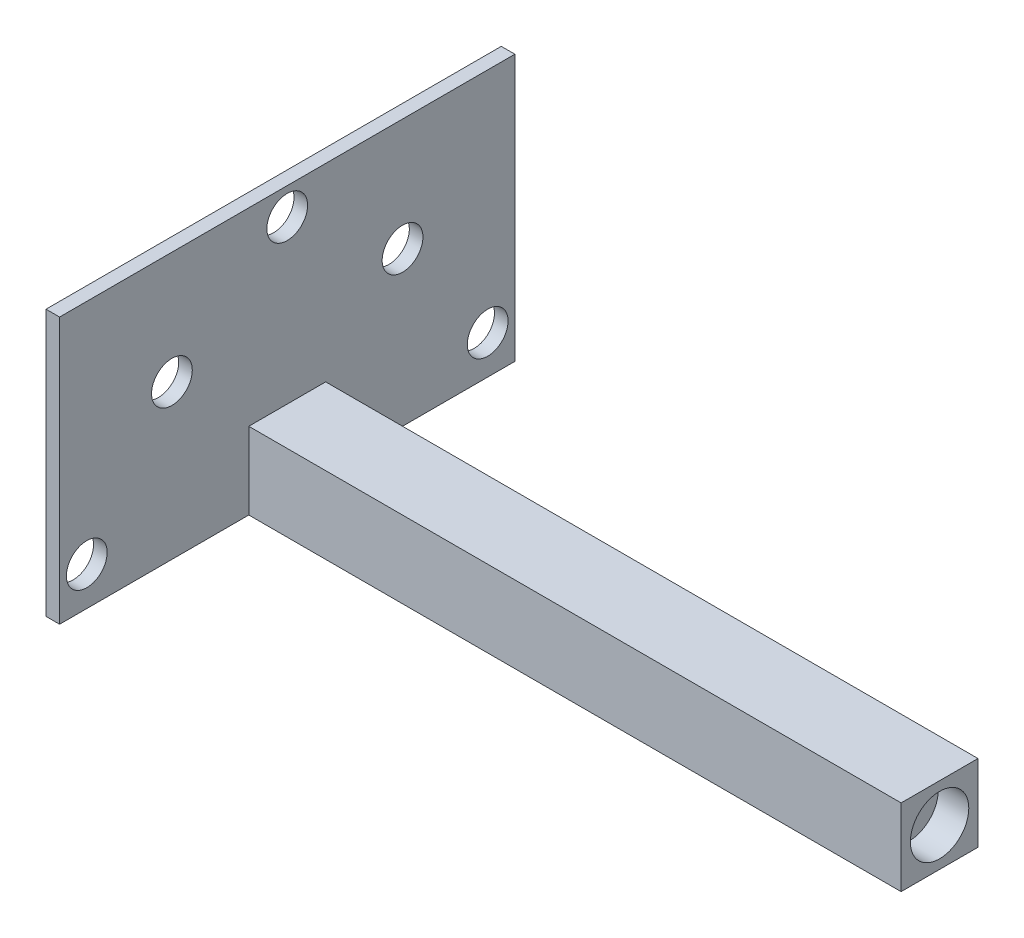
SolidWorks part; units mm, degrees
ref_plane "Front Plane" through (0, 0, 0) normal (0, 0, 1) x (1, 0, 0)
ref_plane "Top Plane" through (0, 0, 0) normal (0, 1, 0) x (1, 0, 0)
ref_plane "Right Plane" through (0, 0, 0) normal (1, 0, 0) x (0, 0, -1)
sketch "Sketch1" plane through (0, 0, 0) normal (1, 0, 0) x (0, 0, -1)
  line L0 (-8.4853, 8.4853) -> (-14.75, 0) construction
  line L1 (-8.4853, 8.4853) -> (0, 14.75) construction
  line L3 (-16.75, -2.8284) -> (16.75, -2.8284)
  line L4 (-16.75, -2.8284) -> (-16.75, 16.75)
  line L5 (-16.75, 16.75) -> (16.75, 16.75)
  line L6 (16.75, -2.8284) -> (16.75, 16.75)
  line L7 (-2.8284, -2.8284) -> (2.8284, -2.8284)
  line L8 (-2.8284, -2.8284) -> (-2.8284, 2.8284)
  line L9 (-2.8284, 2.8284) -> (2.8284, 2.8284)
  line L10 (2.8284, -2.8284) -> (2.8284, 2.8284)
  circle A0 centre (0, 0) radius 14.75 construction
  circle A1 centre (0, 14.75) radius 1.5
  circle A2 centre (0, 0) radius 14.75 construction
  circle A3 centre (14.75, 0) radius 1.5
  circle A4 centre (0, 0) radius 14.75 construction
  circle A5 centre (0, -14.75) radius 1.5 construction
  circle A6 centre (0, 0) radius 14.75 construction
  circle A7 centre (-14.75, 0) radius 1.5
  circle A8 centre (0, 0) radius 12 construction
  circle A9 centre (-8.4853, 8.4853) radius 1.5
  circle A10 centre (8.4853, 8.4853) radius 1.5
  circle A11 centre (8.4853, -8.4853) radius 1.5 construction
  circle A12 centre (-8.4853, -8.4853) radius 1.5 construction
  circle A13 centre (0, 0) radius 4 construction
  point P16 (0, 0)
  point P27 (0, 0)
  dimension "D1" = 4
  dimension "D2" = 4
  dimension "D3" = 2
  dimension "D6" = 3
  dimension "D7" = 8
  dimension "D8" = 29.5
  dimension "D9" = 24
  dimension "D4" = 2
  dimension "D5" = 2
extrude "Boss-Extrude1" add sketch "Sketch1" along normal blind 1 contours L3 L6 L5 L4 A10 A9 A7 A3 A1 | L3 L10 L9 L8 region at (0, 7.3763, 0) region at (0, 0, 0)
extrude "Boss-Extrude2" add sketch "Sketch1<3>" along normal blind 49 contours L3 L10 L9 L8 region at (0, 0, 0)
sketch "Sketch1<3>" plane through (0, 0, 0) normal (1, 0, 0) x (0, 0, -1) same geometry as "Sketch1"
sketch "Sketch3" plane through (49, 0, 0) normal (1, 0, 0) x (0, 0, -1)
  circle A1 centre (0, 0) radius 2.15
extrude "Cut-Extrude1" cut sketch "Sketch3" against normal blind 2.25 contours A1
